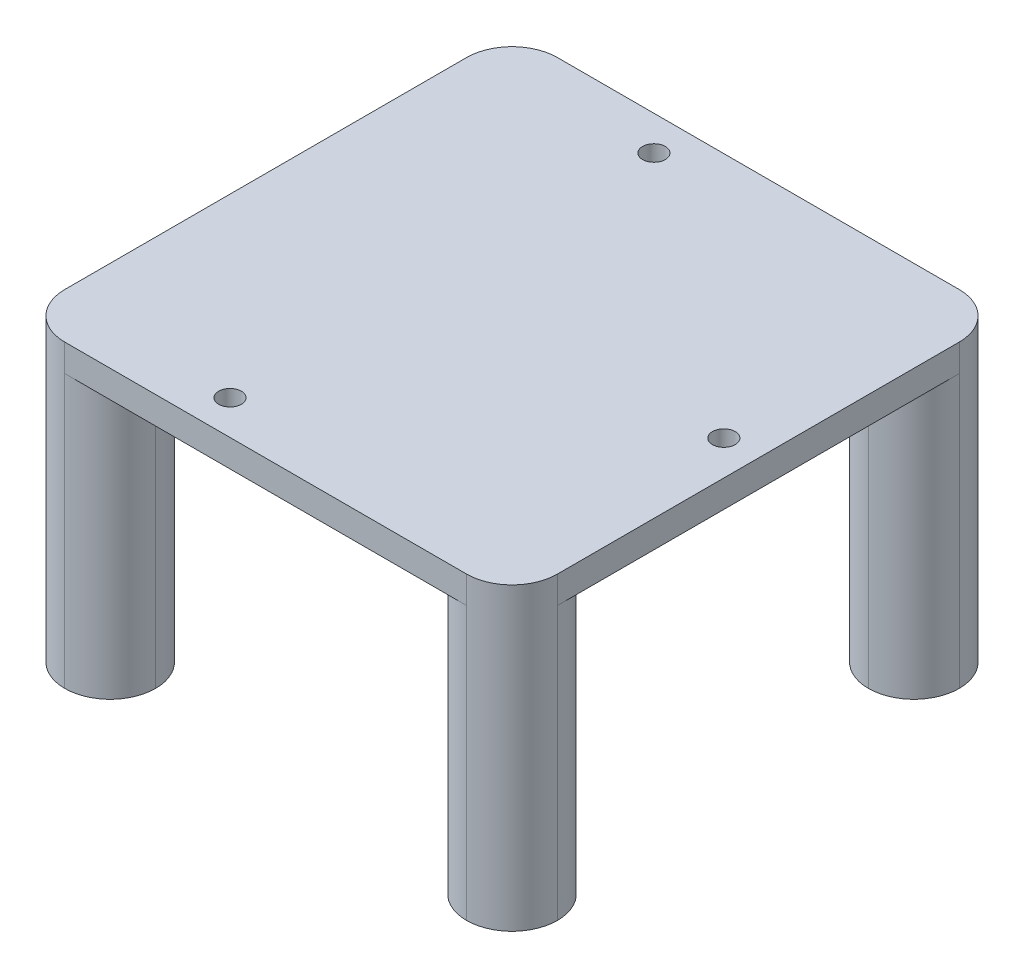
SolidWorks part; units mm, degrees
ref_plane "Front Plane" through (0, 0, 0) normal (0, 0, 1) x (1, 0, 0)
ref_plane "Top Plane" through (0, 0, 0) normal (0, 1, 0) x (1, 0, 0)
ref_plane "Right Plane" through (0, 0, 0) normal (1, 0, 0) x (0, 0, -1)
sketch "Sketch1" plane through (0, 0, 0) normal (0, 1, 0) x (1, 0, 0)
  line L0 (19.4, 50.415) -> (19.4, 3.785) construction
  line L1 (0, 0) -> (54.2, 0)
  line L2 (0, 0) -> (0, 54.2)
  line L3 (0, 54.2) -> (54.2, 54.2)
  line L4 (54.2, 0) -> (54.2, 54.2)
  line L5 (19.4, 27.1) -> (50.4, 27.1) construction
  line L6 (0, 54.2) -> (19.4, 50.415) construction
  line L7 (0, 0) -> (19.4, 3.785) construction
  circle A0 centre (19.4, 50.415) radius 1.25
  circle A1 centre (19.4, 3.785) radius 1.25
  circle A2 centre (50.4, 27.1) radius 1.25
  dimension "D1" = 46.63
  dimension "D4" = 2.5
  dimension "D2" = 31
  dimension "D3" = 54.2
  dimension "D5" = 54.2
  dimension "D6" = 3.8
extrude "Boss-Extrude1" add sketch "Sketch1" along normal blind 3
sketch "Sketch2" plane through (0, 0, 0) normal (0, -1, 0) x (1, 0, 0)
  line L1 (0, 0) -> (10, 0)
  line L2 (0, 0) -> (0, -10)
  line L3 (0, -10) -> (10, -10)
  line L4 (10, 0) -> (10, -10)
  line L5 (54.2, 0) -> (44.2, 0)
  line L6 (54.2, 0) -> (54.2, -10)
  line L7 (54.2, -10) -> (44.2, -10)
  line L8 (44.2, 0) -> (44.2, -10)
  line L9 (0, -54.2) -> (10, -54.2)
  line L10 (0, -54.2) -> (0, -44.2)
  line L11 (0, -44.2) -> (10, -44.2)
  line L12 (10, -54.2) -> (10, -44.2)
  line L13 (54.2, -54.2) -> (44.2, -54.2)
  line L14 (54.2, -54.2) -> (54.2, -44.2)
  line L15 (54.2, -44.2) -> (44.2, -44.2)
  line L16 (44.2, -54.2) -> (44.2, -44.2)
  dimension "D1" = 10
extrude "Boss-Extrude2" add sketch "Sketch2" along normal blind 30
fillet "Fillet1" radius 5 16 edges at (0, -13.5, 0) (0, -13.5, -54.2) (54.2, -13.5, -54.2) (54.2, -13.5, 0) (10, -15, -10) (10, -15, -54.2) (54.2, -15, -10) (44.2, -15, -10) (0, -15, -10) (0, -15, -44.2) (10, -15, -44.2) (54.2, -15, -44.2) (44.2, -15, -54.2) (44.2, -15, -44.2) (44.2, -15, 0) (10, -15, 0)
sketch "Sketch5" plane through (0, -30, 0) normal (0, -1, 0) x (1, 0, 0)
  circle A0 centre (49.2, -5) radius 2.6
  circle A1 centre (49.2, -49.2) radius 2.6
  circle A2 centre (5, -49.2) radius 2.6
  circle A3 centre (5, -5) radius 2.6
  arc A4 (5, -44.2) -> (0, -49.2) centre (5, -49.2) ccw construction
  point P11 (7, -47.4407)
  dimension "D1" = 5.2
extrude "Cut-Extrude1" cut sketch "Sketch5" against normal blind 4
